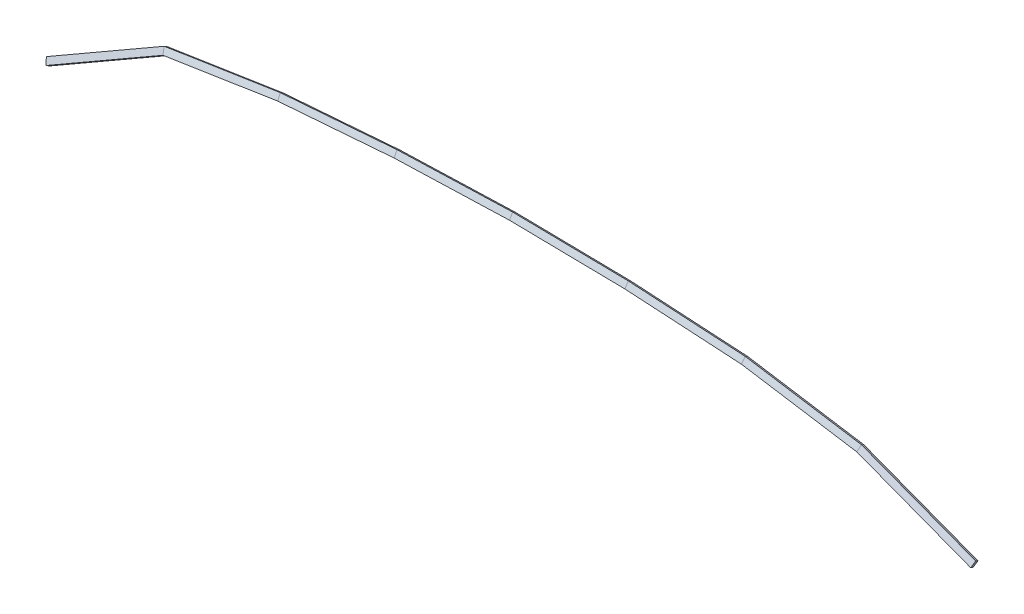
SolidWorks part; units mm, degrees
ref_plane "Front Plane" through (0, 0, 0) normal (0, 0, 1) x (1, 0, 0)
ref_plane "Top Plane" through (0, 0, 0) normal (0, 1, 0) x (1, 0, 0)
ref_plane "Right Plane" through (0, 0, 0) normal (1, 0, 0) x (0, 0, -1)
sketch "Sketch1" plane through (0, 0, 133.35) normal (0, 0, 1) x (1, 0, 0)
  line L0 (-591.5546, -51.2435) -> (-784.0716, -162.1174) construction
  line L1 (-402.166, -22.0956) -> (-591.5546, -51.2435) construction
  line L2 (-211.416, -7.5123) -> (-402.166, -22.0956) construction
  line L3 (-22.6652, -1.2703) -> (-211.416, -7.5123) construction
  line L4 (-22.6652, -1.2703) -> (166.1651, -4.2609) construction
  line L5 (166.1651, -4.2609) -> (357.1251, -15.5363) construction
  line L6 (357.1251, -15.5363) -> (546.7752, -45.5381) construction
  line L7 (546.7752, -45.5381) -> (733.4834, -116.6542) construction
  line L16 (-591.5546, -51.2435) -> (-784.0716, -162.1174)
  line L17 (-402.166, -22.0956) -> (-591.5546, -51.2435)
  line L18 (-211.416, -7.5123) -> (-402.166, -22.0956)
  line L19 (-22.6652, -1.2703) -> (-211.416, -7.5123)
  line L20 (-22.6652, -1.2703) -> (166.1651, -4.2609)
  line L21 (166.1651, -4.2609) -> (357.1251, -15.5363)
  line L22 (357.1251, -15.5363) -> (546.7752, -45.5381)
  line L23 (546.7752, -45.5381) -> (733.4834, -116.6542)
sketch "Sketch2" plane through (0, 0, 0) normal (1, 0, 0) x (0, 0, -1)
  line L0 (-133.35, -1.6389) -> (-128.7526, -4.2932)
  line L1 (-128.7526, -4.2932) -> (-133.9342, -13.268)
  line L2 (-133.9342, -13.268) -> (-138.5316, -10.6137)
  line L3 (-138.5316, -10.6137) -> (-133.35, -1.6389)
  line L4 (-133.35, -1.2703) -> (-133.35, -4.2609) construction
  line L5 (-133.35, -1.6389) -> (-133.35, 7.2562) construction
  dimension "D1" = 5.3086
  dimension "D2" = 10.3632
  dimension "D3" = 30
sweep "Sweep1" add profiles "Sketch2" path "Sketch1"
sketch "Sketch3" plane through (71.2494, 5.8413, 0) normal (0.9999, -0.0158, 0) x (0, 0, -1)
  line L0 (-129.5466, -23.8379) -> (-107.6288, -61.8006) construction
  line L1 (-101.7905, -64.9756) -> (-102.1295, -64.9756) construction
  line L2 (-101.7905, -59.6543) -> (-101.7905, -64.9756) construction
  line L3 (-101.7905, -59.6543) -> (-106.8705, -59.6543) construction
  line L4 (-106.8705, -54.5743) -> (-106.8705, -59.6543) construction
  line L5 (-106.8705, -54.5743) -> (-101.7905, -54.5743) construction
  line L6 (-101.7905, -49.7991) -> (-101.7905, -54.5743) construction
  line L7 (-101.7905, -49.7991) -> (-99.2505, -49.7991) construction
  line L8 (-138.7918, -17.6509) -> (-133.4197, -8.3473) construction
  line L9 (-133.4197, -8.3473) -> (-128.4924, -11.1917) construction
  line L10 (-128.4924, -11.1917) -> (-133.8645, -20.4954) construction
  line L12 (-138.7918, -17.6509) -> (-141.1886, -19.0345) construction
  line L13 (-151.1366, -9.8679) -> (-145.86, -9.8679) construction
  line L14 (-146.0566, -7.3279) -> (-153.6766, -7.3279) construction
  line L15 (-146.0566, -7.3279) -> (-126.7512, -7.3279) construction
  line L16 (-126.7512, -23.5995) -> (-126.7512, -7.3279) construction
  line L23 (-99.2505, -49.9896) -> (-99.2505, -48.5291) construction
  line L24 (-100.5205, -47.2591) -> (-113.0914, -47.2591) construction
  line L25 (-113.0914, -47.2591) -> (-126.7512, -23.5995) construction
  line L26 (-133.8645, -20.4954) -> (-133.8646, -23.2632) construction
  line L31 (-129.5466, -23.8379) -> (-107.6288, -61.8006)
  line L32 (-101.7905, -64.9756) -> (-102.1295, -64.9756)
  line L33 (-101.7905, -59.6543) -> (-101.7905, -64.9756)
  line L34 (-101.7905, -59.6543) -> (-106.8705, -59.6543)
  line L35 (-106.8705, -54.5743) -> (-106.8705, -59.6543)
  line L36 (-106.8705, -54.5743) -> (-101.7905, -54.5743)
  line L37 (-101.7905, -49.7991) -> (-101.7905, -54.5743)
  line L38 (-101.7905, -49.7991) -> (-99.2505, -49.7991)
  line L39 (-138.7918, -17.6509) -> (-133.4197, -8.3473)
  line L40 (-133.4197, -8.3473) -> (-128.4924, -11.1917)
  line L41 (-128.4924, -11.1917) -> (-133.8645, -20.4954)
  line L43 (-138.7918, -17.6509) -> (-141.1886, -19.0345)
  line L44 (-151.1366, -9.8679) -> (-145.86, -9.8679)
  line L45 (-146.0566, -7.3279) -> (-153.6766, -7.3279)
  line L46 (-146.0566, -7.3279) -> (-126.7512, -7.3279)
  line L47 (-126.7512, -23.5995) -> (-126.7512, -7.3279)
  line L54 (-99.2505, -49.7991) -> (-99.2505, -48.5291)
  line L55 (-100.5205, -47.2591) -> (-113.0914, -47.2591)
  line L56 (-113.0914, -47.2591) -> (-126.7512, -23.5995)
  line L57 (-133.8645, -20.4954) -> (-133.8646, -23.2632)
  arc A0 (-107.6288, -61.8006) -> (-102.1295, -64.9756) centre (-102.1295, -58.6256) ccw construction
  arc A1 (-145.86, -9.8679) -> (-141.1886, -19.0345) centre (-129.5466, -7.3279) ccw construction
  arc A2 (-153.6766, -7.3279) -> (-151.1366, -9.8679) centre (-151.1366, -7.3279) ccw construction
  arc A3 (-99.2505, -48.5291) -> (-100.5205, -47.2591) centre (-100.5205, -48.5291) ccw construction
  arc A4 (-133.8646, -23.2632) -> (-126.7512, -23.5995) centre (-129.5466, -7.3279) ccw construction
  arc A5 (-107.6288, -61.8006) -> (-102.1295, -64.9756) centre (-102.1295, -58.6256) ccw
  arc A6 (-145.86, -9.8679) -> (-141.1886, -19.0345) centre (-129.5466, -7.3279) ccw
  arc A7 (-153.6766, -7.3279) -> (-151.1366, -9.8679) centre (-151.1366, -7.3279) ccw
  arc A8 (-99.2505, -48.5291) -> (-100.5205, -47.2591) centre (-100.5205, -48.5291) ccw
  arc A9 (-133.8646, -23.2632) -> (-129.5466, -23.8379) centre (-129.5466, -7.3279) ccw
